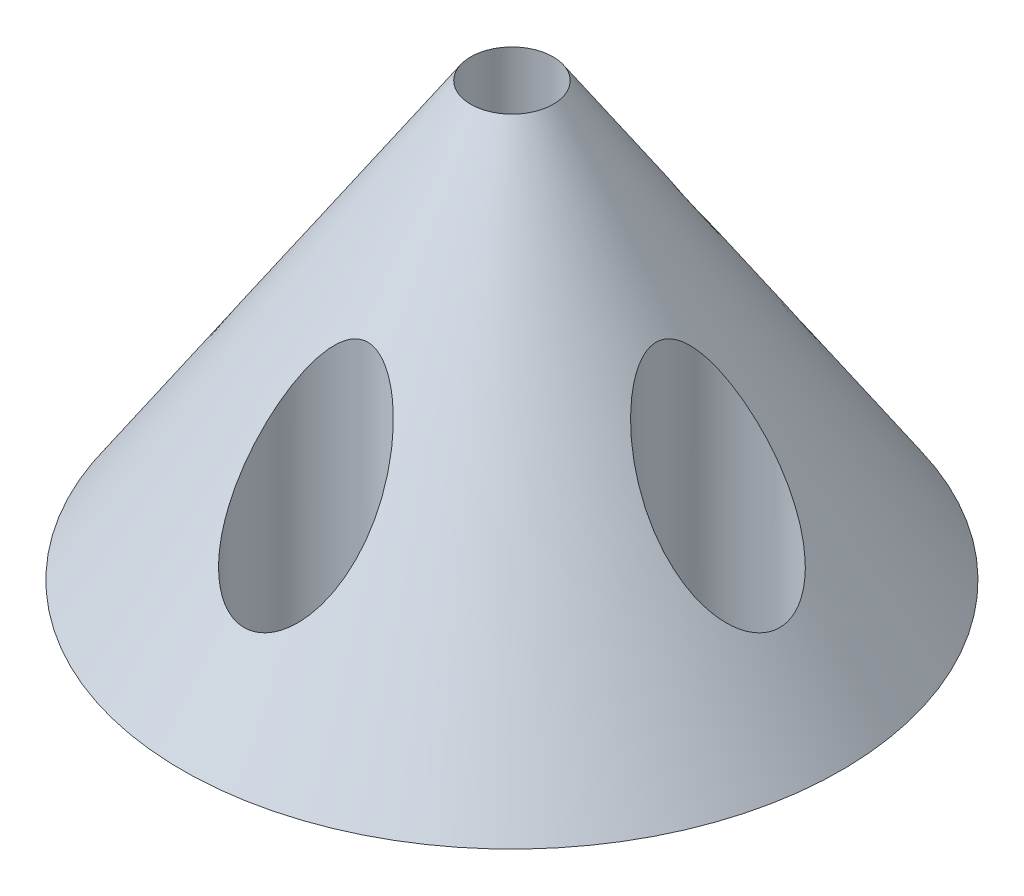
SolidWorks part; units mm, degrees
ref_plane "Front Plane" through (0, 0, 0) normal (0, 0, 1) x (1, 0, 0)
ref_plane "Top Plane" through (0, 0, 0) normal (0, 1, 0) x (1, 0, 0)
ref_plane "Right Plane" through (0, 0, 0) normal (1, 0, 0) x (0, 0, -1)
sketch "Sketch1" plane through (0, 0, 0) normal (1, 0, 0) x (0, 0, -1)
  line L0 (0, -11.2606) -> (0, 11.2606) construction
  line L1 (0, 0) -> (4, 0)
  line L2 (0, 6) -> (0, 0)
  line L3 (0, 6) -> (4, 0)
  point P2 (0, 0)
  dimension "D1" = 6
  dimension "D2" = 4
revolve "Revolve1" add sketch "Sketch1" angle 360 about L0
sketch "Sketch3" plane through (0, 0, 0) normal (0, -1, 0) x (1, 0, 0)
  line L0 (0, -1.5) -> (0, -3.5) construction
  line L1 (0, 1.5) -> (0, -1.5) construction
  line L2 (-3.5, 0) -> (-1.5, 0) construction
  line L3 (-1.5, 0) -> (1.5, 0) construction
  circle A0 centre (0, 0) radius 3.5
  circle A1 centre (0, 0) radius 1.5
  circle A2 centre (0, -2.5) radius 0.75
  circle A3 centre (0, 2.5) radius 0.75
  circle A4 centre (-2.5, 0) radius 0.75
  circle A5 centre (2.5, 0) radius 0.75
  circle A6 centre (0, 0) radius 0.5
  dimension "D1" = 7
  dimension "D2" = 3
  dimension "D3" = 1.5
  dimension "D4" = 1.5
  dimension "D5" = 1
extrude "Cut-Extrude1" cut sketch "Sketch3" against normal blind 6 contours A4 | A2 | A5 | A6 | A3 | A5 region at (0, 0, -2.5) region at (0, 0, 2.5) region at (-2.5, 0, 0) region at (2.5, 0, 0) region at (0, 0, 0)
extrude "Cut-Extrude2" cut sketch "Sketch3<3>" against normal blind 2 contours A1
sketch "Sketch3<3>" plane through (0, 0, 0) normal (0, -1, 0) x (1, 0, 0) same geometry as "Sketch3"
